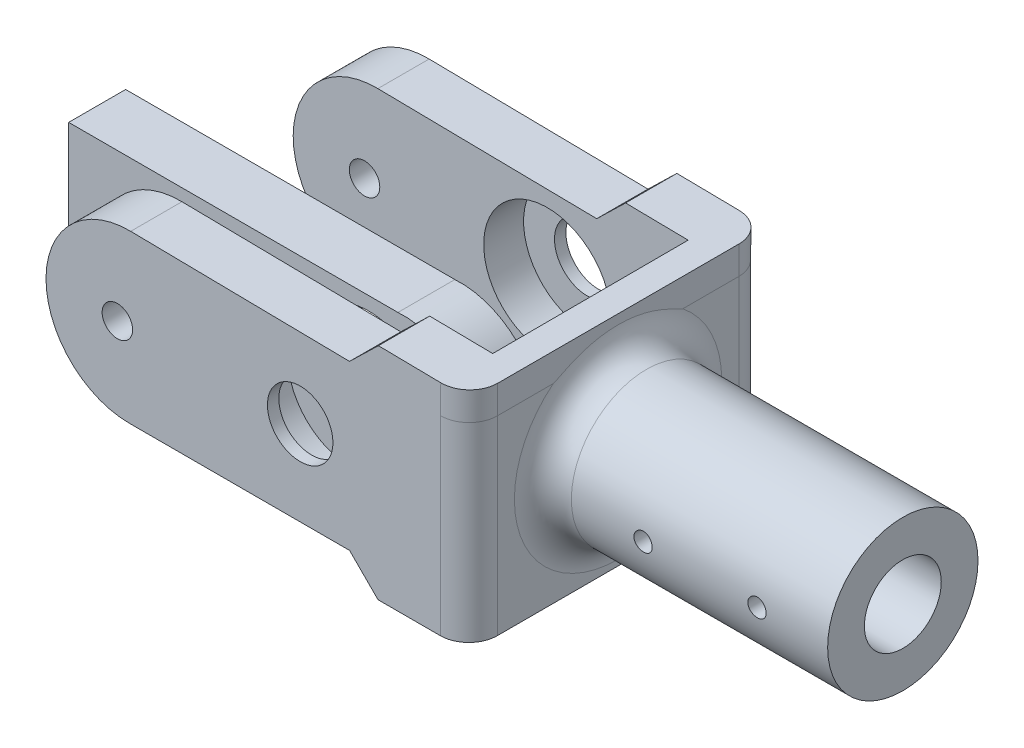
SolidWorks part; units mm, degrees
ref_plane "Front Plane" through (0, 0, 0) normal (0, 0, 1) x (1, 0, 0)
ref_plane "Top Plane" through (0, 0, 0) normal (0, 1, 0) x (1, 0, 0)
ref_plane "Right Plane" through (0, 0, 0) normal (1, 0, 0) x (0, 0, -1)
sketch "Sketch2" plane through (0, 0, 0) normal (0, 0, 1) x (1, 0, 0)
  line L0 (32.0567, -28.433) -> (59.7484, -28.433)
  line L1 (57.8058, 0) -> (0, 0)
  line L2 (0, 0) -> (0, -28.433)
  line L3 (32.0567, -28.433) -> (0, -28.433)
  line L4 (0, -14.2165) -> (72.9936, -13.2452) construction
  arc A0 (59.7484, -28.433) -> (57.8058, 0) centre (58.7771, -14.2165) ccw
  circle A1 centre (20.5461, -13.9431) radius 2.675
  circle A2 centre (52.6439, -13.516) radius 11.175
  dimension "D1" = 22.35
  dimension "D2" = 5.35
extrude "Boss-Extrude1" add sketch "Sketch2" against normal blind 10
ref_plane "Plane1" through (0, 0, 3) normal (0, 0, 1) x (1, 0, 0)
sketch "Sketch3" plane through (0, 0, 3) normal (0, 0, 1) x (1, 0, 0)
  line L2 (0, -28.433) -> (59.7484, -28.433) construction
  line L4 (82.2553, -28.433) -> (82.2553, -0.003)
  line L5 (82.2553, -0.003) -> (26.3169, 0.8251)
  line L6 (26.3169, 0.8251) -> (26.3169, -28.433) construction
  line L7 (26.3169, -28.433) -> (82.2553, -28.433)
  line L9 (22.8882, 0.8759) -> (26.3169, 0.8251)
  line L10 (26.3169, -28.433) -> (22.6713, -28.433)
  circle A0 centre (20.5461, -13.9431) radius 2.675
  circle A1 centre (52.6439, -13.516) radius 11.175 construction
  arc A2 (22.8882, 0.8759) -> (22.6713, -28.433) centre (22.6713, -13.7778) ccw
  dimension "D2" = 22.35
  dimension "D3" = 5.35
  dimension "D1" = 28.43
extrude "Boss-Extrude2" add sketch "Sketch3" along normal blind 9 separate body
sketch "Sketch4" plane through (0, 0, 0) normal (0, 1, 0) x (1, 0, 0)
  line L0 (82.2553, -3) -> (82.2553, 37.4) construction
  line L1 (82.2553, 37.4) -> (82.2553, 68.2284) construction
  line L3 (-15.6564, -3) -> (15.6564, -3) construction
  line L5 (82.2553, 37.4) -> (82.2553, -3)
  line L6 (82.2553, -3) -> (77.3852, -3)
  line L7 (82.2553, 37.4) -> (77.3852, 37.4)
  line L8 (77.3852, 37.4) -> (77.3852, -3)
  dimension "D1" = 40.4
extrude "Boss-Extrude3" add sketch "Sketch4" against normal up to vertex (28.433 mm away) up to point (82.2553, -28.433, 3)
ref_plane "Plane3" through (0, 0, -8.2) normal (0, 0, 1) x (1, 0, 0)
sketch "Sketch5" plane through (0, 0, 3) normal (0, 0, 1) x (1, 0, 0)
  line L0 (82.2553, -28.433) -> (82.2553, -0.003) construction
  line L1 (22.6713, -28.433) -> (82.2553, -28.433) construction
  line L2 (82.2553, -0.003) -> (22.8882, 0.8759) construction
  line L3 (82.2553, -28.433) -> (82.2553, -0.003)
  line L4 (22.6713, -28.433) -> (82.2553, -28.433)
  line L5 (82.2553, -0.003) -> (22.8882, 0.8759)
  circle A0 centre (20.5461, -13.9431) radius 2.675 construction
  arc A1 (22.8882, 0.8759) -> (22.6713, -28.433) centre (22.6713, -13.7778) ccw construction
  circle A2 centre (20.5461, -13.9431) radius 2.675
  arc A3 (22.8882, 0.8759) -> (22.6713, -28.433) centre (22.6713, -13.7778) ccw
sketch "Sketch6" plane through (0, 0, 12) normal (0, 0, -1) x (-1, 0, 0)
  circle A0 centre (-52.6439, -13.516) radius 11.175 construction
  circle A3 centre (-52.6439, -13.516) radius 11.175
extrude "Boss-Extrude6" add sketch "Sketch5" against normal blind 9 from offset 34.4 offset against normal yes
ref_plane "Plane5" through (0.018, 1.2145, 0) normal (0.0148, 0.9999, 0) x (0.9999, -0.0148, 0)
sketch "Sketch14" plane through (0.018, 1.2145, 0) normal (0.0148, 0.9999, 0) x (0.9999, -0.0148, 0)
  line L0 (56.2983, 40.4) -> (82.2464, 40.4)
  line L1 (82.2464, 40.4) -> (22.8728, 40.4) construction
  line L2 (82.2464, 40.4) -> (82.2464, -12)
  line L3 (82.2464, -12) -> (56.2983, -12)
  line L4 (56.2983, -12) -> (56.2983, -3)
  line L5 (56.2983, 31.4) -> (77.2788, 31.4)
  line L6 (82.0427, 31.4) -> (22.8728, 31.4) construction
  line L7 (77.3654, -3) -> (56.2983, -3)
  line L10 (82.0427, -3) -> (22.8728, -3) construction
  line L11 (77.3654, -3) -> (77.2788, 31.4)
  line L12 (56.2983, 31.4) -> (56.2983, 40.4)
  dimension "D1" = 21.0671
extrude "Boss-Extrude8" add sketch "Sketch14" along normal blind 5
sketch "Sketch16" plane through (0, -28.433, 0) normal (0, -1, 0) x (1, 0, 0)
  line L0 (77.3852, 3) -> (56.3152, 3)
  line L1 (22.6713, 3) -> (77.3852, 3) construction
  line L2 (56.3152, 3) -> (56.3152, 12)
  line L3 (22.6713, 12) -> (82.2553, 12) construction
  line L4 (56.3152, 12) -> (82.2553, 12)
  line L5 (82.2553, 12) -> (82.2553, -40.4)
  line L6 (82.2553, -40.4) -> (56.3152, -40.4)
  line L7 (22.6713, -40.4) -> (82.2553, -40.4) construction
  line L8 (56.3152, -40.4) -> (56.3152, -31.4)
  line L9 (22.6713, -31.4) -> (77.3852, -31.4) construction
  line L10 (56.3152, -31.4) -> (77.3852, -31.4)
  line L11 (77.3852, -31.4) -> (77.3852, 3)
  dimension "D1" = 21.07
extrude "Boss-Extrude14" add sketch "Sketch16" along normal blind 5
extrude "Cut-Extrude4" cut sketch "Sketch6" against normal blind 7 from surface starting at face at (23.2211, -13.9431, 3)
sketch "Sketch9" plane through (0, 0, -40.4) normal (0, 0, 1) x (1, 0, 0)
  circle A0 centre (52.6439, -13.516) radius 11.175 construction
  circle A1 centre (52.6439, -13.516) radius 11.175
extrude "Cut-Extrude5" cut sketch "Sketch9" against normal blind 7 from surface starting at face at (23.2211, -13.9431, -31.4)
sketch "Sketch10" plane through (0, 0, 12) normal (0, 0, 1) x (1, 0, 0)
  circle A0 centre (52.6439, -13.516) radius 5.75
extrude "Cut-Extrude6" cut sketch "Sketch10" against normal through all both and the other way through all
sketch "Sketch11" plane through (82.2553, 0, 0) normal (1, 0, 0) x (0, 0, -1)
  circle A0 centre (14.2, -14.218) radius 13.2
  circle A1 centre (14.2, -14.218) radius 6.75
  dimension "D1" = 26.4
  dimension "D2" = 13.5
extrude "Boss-Extrude10" add sketch "Sketch11" along normal blind 50
fillet "Fillet5" radius 5 1 edges at (82.2553, -14.218, -1)
chamfer "Chamfer2" distance 10 angle 45 4 edges at (56.3152, -33.433, -35.9) (56.3152, -33.433, 7.5) (56.3842, 5.3805, 7.5) (56.3842, 5.3805, -35.9)
fillet "Fillet6" radius 5 6 edges at (82.2923, 2.4967, 12) (82.2923, 2.4967, -40.4) (82.2553, -16.718, 12) (82.2553, -16.718, -40.4) (77.3852, -16.7165, -31.4) (77.3852, -16.7165, 3)
ref_plane "Plane8" through (0, 0, -40.4) normal (0, 0, -1) x (-1, 0, 0)
sketch "Sketch17" plane through (0, 0, -40.4) normal (0, 0, -1) x (-1, 0, 0)
  line L0 (-132.2553, -1.3703) -> (-132.2553, -27.418) construction
  line L1 (-132.2553, -1.018) -> (-132.2553, -27.418) construction
  line L2 (-132.2553, -14.3942) -> (-87.734, -14.3942) construction
  circle A0 centre (-119.8421, -14.3942) radius 1.6
  circle A1 centre (-99.8421, -14.3942) radius 1.6
  dimension "D1" = 20
extrude "Cut-Extrude8" cut sketch "Sketch17" against normal through all both and the other way through all
